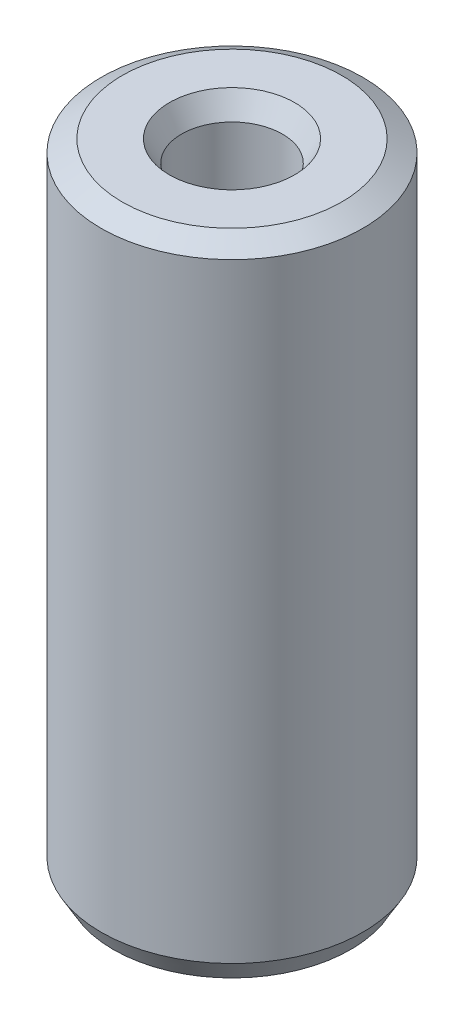
SolidWorks part; units mm, degrees
ref_plane "Front Plane" through (0, 0, 0) normal (0, 0, 1) x (1, 0, 0)
ref_plane "Top Plane" through (0, 0, 0) normal (0, 1, 0) x (1, 0, 0)
ref_plane "Right Plane" through (0, 0, 0) normal (1, 0, 0) x (0, 0, -1)
sketch "Sketch1" plane through (0, 0, 0) normal (0, 1, 0) x (1, 0, 0)
  circle A0 centre (0, 0) radius 32.5
  dimension "SLEEVE_OD" = 65
extrude "Boss-Extrude1" add sketch "Sketch1" along normal blind 159.6661
sketch "Sketch2" plane through (0, 0, 0) normal (0, 1, 0) x (1, 0, 0)
  circle A0 centre (0, 0) radius 12.5265
  dimension "BORE_D" = 25.053
extrude "Cut-Extrude1" cut sketch "Sketch2" along normal through all
chamfer "Chamfer1" distance 3.0343 angle 60 4 edges at (0, 159.6661, 12.5265) (0, 0, 12.5265) (0, 0, 32.5) (0, 159.6661, 32.5) first distance on face at (0, 159.6661, 12.5265) first distance on face at (0, 0, 12.5265) first distance on face at (0, 159.6661, 32.5)
